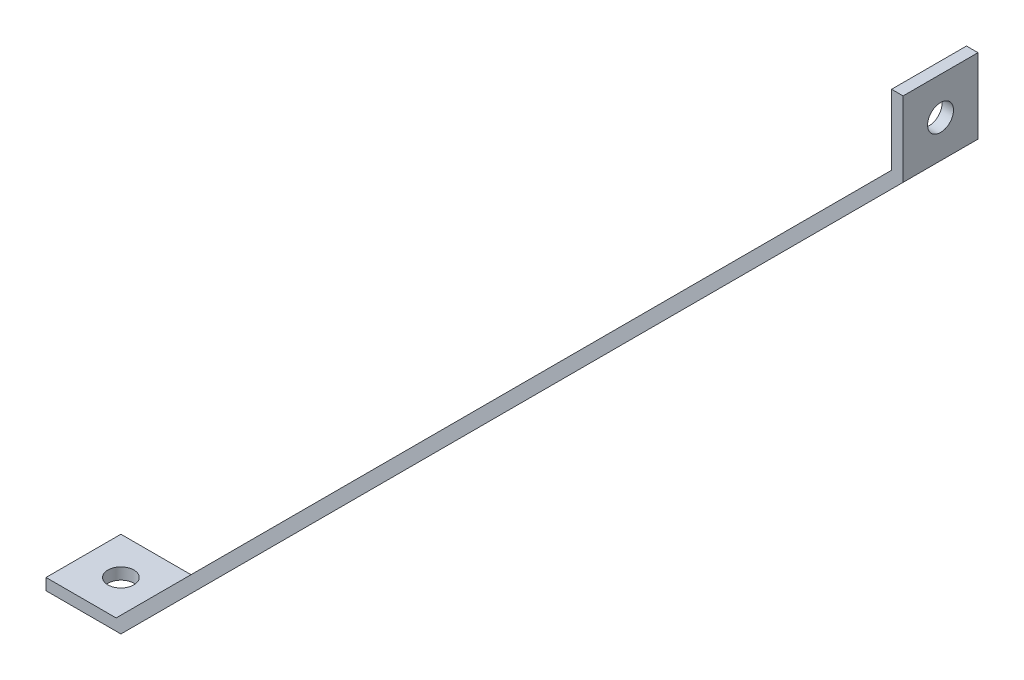
SolidWorks part; units mm, degrees
ref_plane "Front Plane" through (0, 0, 0) normal (0, 0, 1) x (1, 0, 0)
ref_plane "Top Plane" through (0, 0, 0) normal (0, 1, 0) x (1, 0, 0)
ref_plane "Right Plane" through (0, 0, 0) normal (1, 0, 0) x (0, 0, -1)
sketch "Sketch1" plane through (0, 0, 0) normal (0, 0, 1) x (1, 0, 0)
  line L0 (-256.8011, -215.5261) -> (-215.5261, -215.5261)
  line L1 (-215.5261, -215.5261) -> (215.5261, 215.5261)
  line L2 (215.5261, 215.5261) -> (215.5261, 256.8011)
  dimension "D1" = 45
  dimension "D2" = 41.275
  dimension "LG" = 609.6
extrude "Extrude-Thin1" add sketch "Sketch1" along normal mid plane 41.275 thin thin type one direction reverse wall 6.35
sketch "Sketch2" plane through (0, -209.1761, 0) normal (0, 1, 0) x (1, 0, 0)
  line L0 (-256.8011, -20.6375) -> (-256.8011, 20.6375) construction
  circle A0 centre (-236.1636, 0) radius 7.1438
  dimension "D1" = 14.2875
  dimension "D2" = 20.6375
extrude "Cut-Extrude1" cut sketch "Sketch2" against normal through all
sketch "Sketch3" plane through (209.1761, 0, 0) normal (-1, 0, 0) x (0, 0, 1)
  line L0 (20.6375, 256.8011) -> (-20.6375, 256.8011) construction
  circle A0 centre (0, 236.1636) radius 7.1437
  dimension "D1" = 14.2875
  dimension "D2" = 20.6375
extrude "Cut-Extrude2" cut sketch "Sketch3" against normal through all
